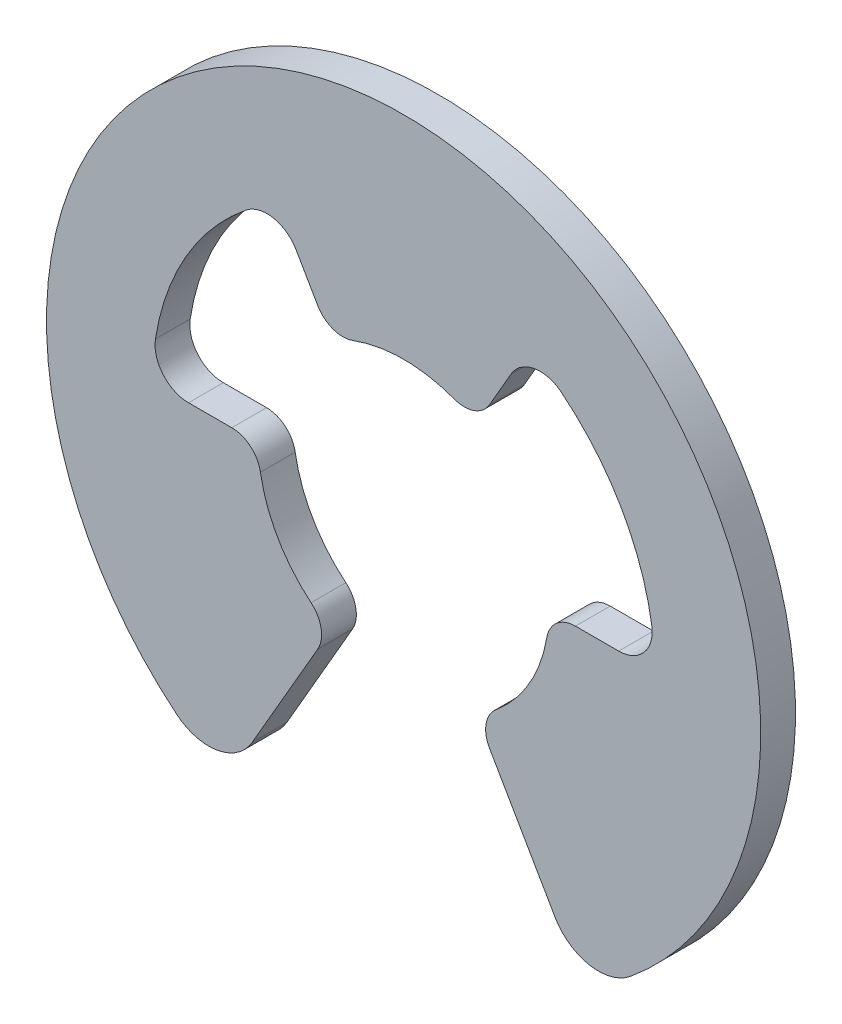
SolidWorks part; units mm, degrees
material "Plain Carbon Steel"
ref_plane "Front Plane" through (0, 0, 0) normal (0, 0, 1) x (1, 0, 0)
ref_plane "Top Plane" through (0, 0, 0) normal (0, 1, 0) x (1, 0, 0)
ref_plane "Right Plane" through (0, 0, 0) normal (1, 0, 0) x (0, 0, -1)
sketch "Sketch1" plane through (0, 0, 0) normal (0, 0, 1) x (1, 0, 0)
  line L0 (-4.0374, -6.9929) -> (-2.2916, -3.9692)
  line L1 (-4.5832, 0) -> (-5.7369, 0)
  line L2 (-2.8684, 4.9683) -> (-2.2916, 3.9692)
  line L3 (2.2916, 3.9692) -> (2.8684, 4.9683)
  line L4 (5.7369, 0) -> (4.5832, 0)
  line L5 (2.2916, -3.9692) -> (4.0374, -6.9929)
  arc A0 (6.0485, -7.358) -> (-6.0485, -7.358) centre (0, 0) ccw
  arc A1 (-6.0485, -7.358) -> (-4.0374, -6.9929) centre (-5.1977, -6.323) ccw
  arc A2 (-2.2916, -3.9692) -> (-2.4688, -2.9848) centre (-2.9625, -3.5818) ccw
  arc A3 (-2.4688, -2.9848) -> (-3.8193, -0.6456) centre (0, 0) cw
  arc A4 (-3.8193, -0.6456) -> (-4.5832, 0) centre (-4.5832, -0.7747) ccw
  arc A5 (-5.7369, 0) -> (-6.6195, 1.0307) centre (-5.7369, 0.8932) cw
  arc A6 (-6.6195, 1.0307) -> (-4.2023, 5.2173) centre (0, 0) cw
  arc A7 (-4.2023, 5.2173) -> (-2.8684, 4.9683) centre (-3.642, 4.5217) cw
  arc A8 (-2.2916, 3.9692) -> (-1.3506, 3.6304) centre (-1.6207, 4.3565) ccw
  arc A9 (-1.3506, 3.6304) -> (1.3506, 3.6304) centre (0, 0) cw
  arc A10 (1.3506, 3.6304) -> (2.2916, 3.9692) centre (1.6207, 4.3565) ccw
  arc A11 (2.8684, 4.9683) -> (4.2023, 5.2173) centre (3.642, 4.5217) cw
  arc A12 (4.2023, 5.2173) -> (6.6195, 1.0307) centre (0, 0) cw
  arc A13 (6.6195, 1.0307) -> (5.7369, 0) centre (5.7369, 0.8932) cw
  arc A14 (4.5832, 0) -> (3.8193, -0.6456) centre (4.5832, -0.7747) ccw
  arc A15 (3.8193, -0.6456) -> (2.4688, -2.9848) centre (0, 0) cw
  arc A16 (2.4688, -2.9848) -> (2.2916, -3.9692) centre (2.9625, -3.5818) ccw
  arc A17 (4.0374, -6.9929) -> (6.0485, -7.358) centre (5.1977, -6.323) ccw
extrude "Boss-Extrude1" add sketch "Sketch1" against normal blind 0.4636 and the other way blind 0.4636
ref_plane "RR XY" through (0, 0, 0) normal (0, 0, 1) x (1, 0, 0)
ref_plane "RR XZ" through (0, 0, 0) normal (0, -1, 0) x (-1, 0, 0)
ref_plane "RR YZ" through (0, 0, 0) normal (1, 0, 0) x (0, 0, -1)
ref_axis "RR X" through (-80.9, 0, 0) along (1, 0, 0)
ref_axis "RR Y" through (0, -50, 0) along (0, 1, 0)
ref_axis "RR Z" through (0, 0, 80.9) along (0, 0, -1)
sketch3d "RR"
  point P0 (0, 0, 0)
